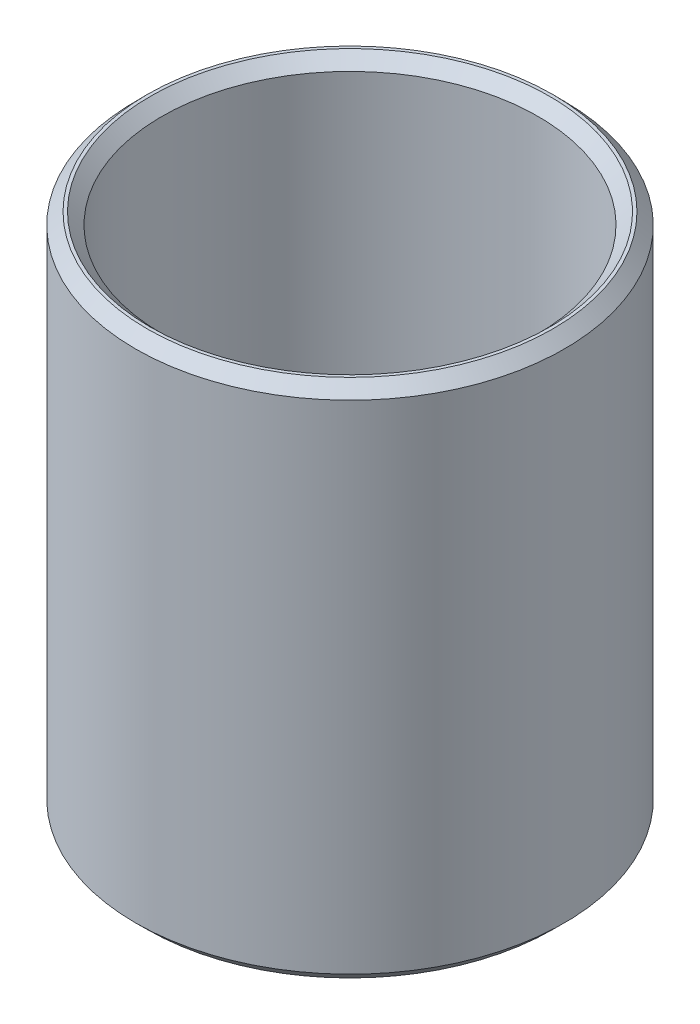
SolidWorks part; units mm, degrees
ref_plane "Front Plane" through (0, 0, 0) normal (0, 0, 1) x (1, 0, 0)
ref_plane "Top Plane" through (0, 0, 0) normal (0, 1, 0) x (1, 0, 0)
ref_plane "Right Plane" through (0, 0, 0) normal (1, 0, 0) x (0, 0, -1)
sketch "Sketch1" plane through (0, 0, 0) normal (0, 1, 0) x (1, 0, 0)
  circle A0 centre (0, 0) radius 32.5
  dimension "SLEEVE_OD" = 65
extrude "Boss-Extrude1" add sketch "Sketch1" along normal blind 78.8467
sketch "Sketch2" plane through (0, 0, 0) normal (0, 1, 0) x (1, 0, 0)
  circle A0 centre (0, 0) radius 28.5107
  dimension "BORE_D" = 57.0213
extrude "Cut-Extrude1" cut sketch "Sketch2" along normal through all
chamfer "Chamfer1" distance 1.768 angle 44.623 4 edges at (0, 78.8467, 28.5107) (0, 0, 28.5107) (0, 0, 32.5) (0, 78.8467, 32.5) first distance on face at (0, 78.8467, 28.5107) first distance on face at (0, 0, 28.5107) first distance on face at (0, 78.8467, 32.5)
